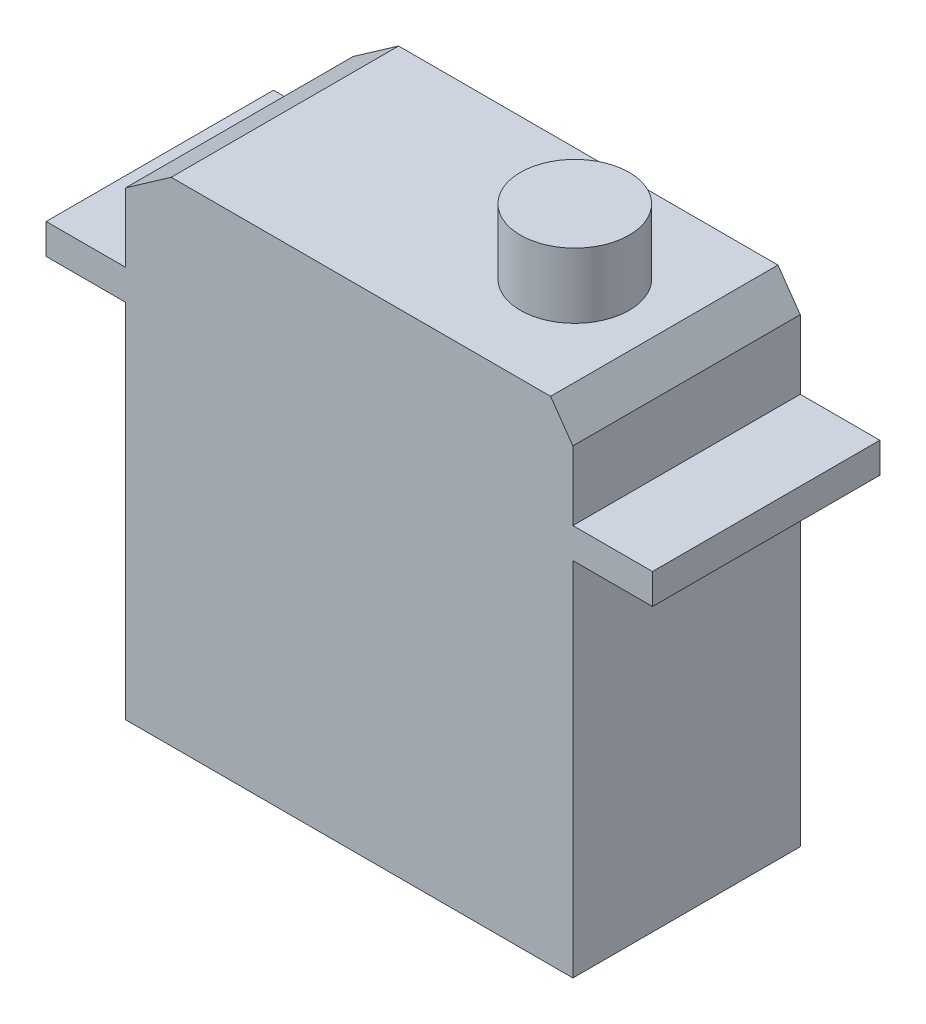
SolidWorks part; units mm, degrees
ref_plane "XY" through (0, 0, 0) normal (0, 0, 1) x (1, 0, 0)
ref_plane "XZ" through (0, 0, 0) normal (0, 1, 0) x (1, 0, 0)
ref_plane "YZ" through (0, 0, 0) normal (1, 0, 0) x (0, 0, -1)
ref_axis "X" through (-88.99, 0, 0) along (1, 0, 0)
ref_axis "Y" through (0, -55, 0) along (0, 1, 0)
ref_axis "Z" through (0, 0, 55) along (0, 0, -1)
sketch "Sketch1" plane through (0, 0, 0) normal (0, 0, 1) x (1, 0, 0)
  line L0 (-14.75, 11.925) -> (-20, 11.925)
  line L1 (-14.75, -11.925) -> (14.75, -11.925)
  line L2 (-14.75, -11.925) -> (-14.75, 11.925)
  line L4 (14.75, -11.925) -> (14.75, 11.925)
  line L5 (-14.75, -11.925) -> (14.75, 11.925) construction
  line L6 (-14.75, 11.925) -> (14.75, -11.925) construction
  line L7 (-20, 11.925) -> (-20, 13.925)
  line L8 (-20, 13.925) -> (-14.75, 13.925)
  line L9 (-14.75, 13.925) -> (-14.75, 18.4744)
  line L10 (-14.75, 18.4744) -> (-11.75, 20.575)
  line L11 (-11.75, 20.575) -> (13.2791, 20.575)
  line L12 (13.2791, 20.575) -> (14.75, 18.4744)
  line L13 (14.75, 18.4744) -> (14.75, 13.925)
  line L14 (14.75, 13.925) -> (20, 13.925)
  line L15 (20, 13.925) -> (20, 11.925)
  line L16 (20, 11.925) -> (14.75, 11.925)
  point P0 (0, 0)
  dimension "D1" = 23.85
  dimension "D2" = 29.5
  dimension "D3" = 8.65
  dimension "D4" = 40
  dimension "D5" = 2
  dimension "D6" = 125
  dimension "D7" = 3
extrude "Boss-Extrude1" add sketch "Sketch1" along normal mid plane 15
sketch "Sketch2" plane through (0, 20.575, 0) normal (0, 1, 0) x (1, 0, 0)
  line L0 (0, 0) -> (14.75, 0) construction
  line L1 (14.75, -7.5) -> (14.75, 7.5) construction
  circle A0 centre (7.375, 0) radius 3.5871
extrude "Boss-Extrude2" add sketch "Sketch2" along normal blind 4.3
